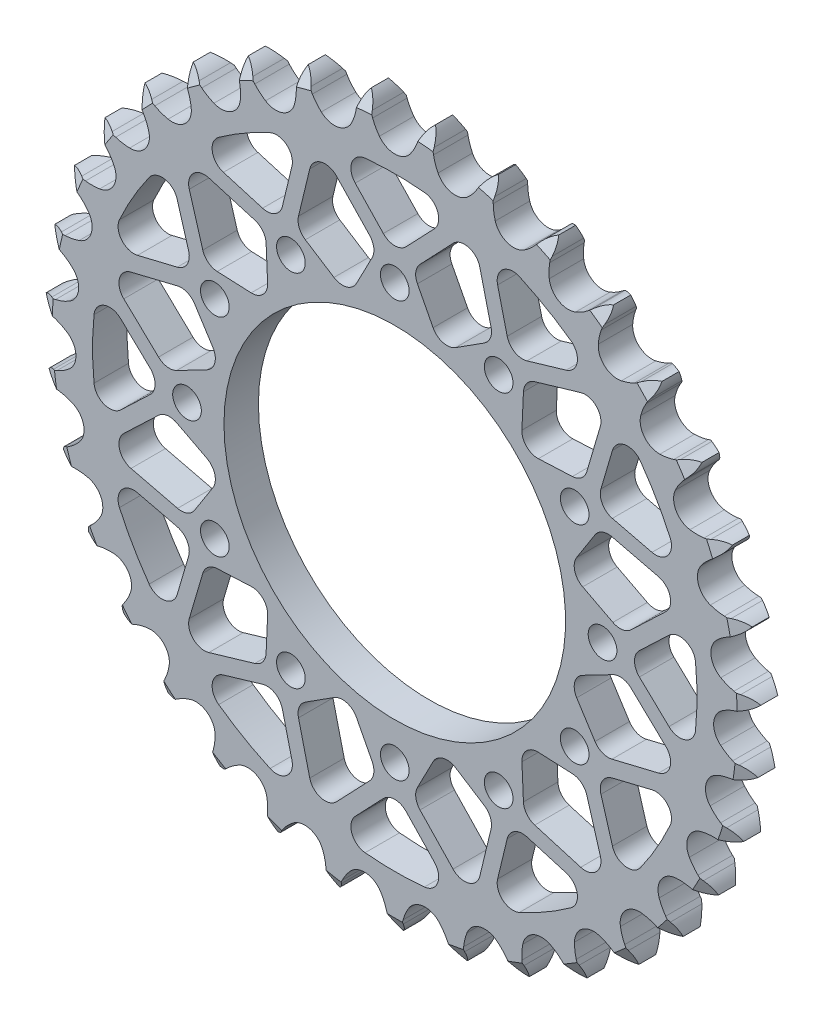
SolidWorks part; units mm, degrees
material "7075-T6 (SN)"
ref_plane "Front Plane" through (0, 0, 0) normal (0, 0, 1) x (1, 0, 0)
ref_plane "Top Plane" through (0, 0, 0) normal (0, 1, 0) x (1, 0, 0)
ref_plane "Right Plane" through (0, 0, 0) normal (1, 0, 0) x (0, 0, -1)
sketch "Work Sketch" plane through (0, 0, 0) normal (0, 0, 1) x (1, 0, 0)
  line L0 (0, 0) -> (0, 160.4542) construction
  line L1 (-112.0919, 70.8395) -> (87.2579, 70.8395) construction
  line L2 (5.0903, 120.8822) -> (5.0903, 112.9699) construction
  line L3 (-12.8497, 74.6356) -> (16.7256, 74.6356) construction
  line L4 (5.0903, 74.6356) -> (-6.074, 66.3097) construction
  line L5 (5.0903, 74.6356) -> (-4.641, 71.0332) construction
  line L6 (-4.641, 71.0332) -> (-6.9559, 77.2865)
  line L7 (-11.5114, 69.8433) -> (-7.1525, 69.8433) construction
  line L8 (-11.0678, 124.7602) -> (-11.0678, 110.2345) construction
  line L9 (0, 0) -> (-3.8324, 42.5811) construction
  circle A0 centre (0, 0) radius 70.8395
  circle A1 centre (0, 70.8395) radius 4.0088
  arc A2 (-4.641, 71.0332) -> (-3.2136, 68.4429) centre (5.0682, 74.6949) ccw
  circle A3 centre (-11.0678, 69.8433) radius 6.4401
  point P23 (-3.2136, 68.4429)
  dimension "D1" = 141.6789
  dimension "D8" = 10.3767
  dimension "D2" = 8.0177
  dimension "D3" = 5.0903
  dimension "D4" = 3.7962
  dimension "D5" = 36.714
  dimension "D6" = 16.4
  dimension "D7" = 10.3767
  dimension "D9" = 0.9961
  dimension "D10" = 11.0678
  dimension "D11" = 5.143
sketch "Teeth Sketch" plane through (0, 0, 0) normal (0, 0, 1) x (1, 0, 0)
  line L0 (5.0282, 72.0792) -> (4.641, 71.0332)
  line L1 (-8.3399, 92.6643) -> (-5.3292, 59.2127) construction
  line L2 (0, 0) -> (-12.1309, 132.2) construction
  line L3 (7.9229, 71.8186) -> (8.1171, 70.7203)
  line L4 (17927.8618, -199194.8588) -> (-17931.6941, 199237.4399) construction
  line L5 (0, 146.3285) -> (0, 56.9858) construction
  line L6 (17.8176, 70.023) -> (17.2498, 69.063)
  line L7 (0, -200000) -> (0, 200160.4542) construction
  line L8 (20.6192, 69.2498) -> (20.6142, 68.1345)
  line L9 (-4.641, 71.0332) -> (-6.9559, 77.2865) construction
  line L10 (43.6371, 57.589) -> (43.2405, 56.5465)
  line L11 (-5.0282, 72.0792) -> (-4.641, 71.0332)
  line L12 (30.0344, 65.7163) -> (29.3043, 64.873)
  line L13 (32.6529, 64.4552) -> (32.4488, 63.3587)
  line L14 (41.2858, 59.2973) -> (40.4169, 58.598)
  line L15 (51.2103, 50.9725) -> (50.2305, 50.4396)
  line L16 (53.2187, 48.8718) -> (52.6424, 47.9169)
  line L17 (59.4888, 41.0094) -> (58.4296, 40.66)
  line L18 (61.0899, 38.5838) -> (60.3523, 37.7472)
  line L19 (65.8553, 29.7283) -> (64.7507, 29.5736)
  line L20 (66.9976, 27.0558) -> (66.1224, 26.3643)
  line L21 (70.1052, 17.4916) -> (68.9907, 17.5366)
  line L22 (70.7519, 14.6581) -> (69.7673, 14.134)
  line L23 (72.1018, 4.6927) -> (71.0133, 4.9361)
  line L24 (72.2322, 1.7893) -> (71.1699, 1.4494)
  line L25 (71.781, -8.2569) -> (70.7534, -7.8232)
  line L26 (71.3909, -11.137) -> (70.2849, -11.2818)
  line L27 (69.1531, -20.9412) -> (68.2195, -20.331)
  line L28 (68.255, -23.7054) -> (67.141, -23.6503)
  line L29 (64.3026, -32.9525) -> (63.493, -32.1853)
  line L30 (62.9254, -35.5118) -> (61.8391, -35.2587)
  line L31 (57.3853, -43.9046) -> (56.7257, -43.0052)
  line L32 (55.5732, -46.1769) -> (54.5496, -45.7339)
  line L33 (48.6237, -53.4456) -> (48.1352, -52.4428)
  line L34 (46.435, -55.3578) -> (45.5069, -54.7392)
  line L35 (38.2992, -61.2688) -> (37.9976, -60.1949)
  line L36 (35.8042, -62.7594) -> (35.0015, -61.985)
  line L37 (26.7437, -67.1227) -> (26.6388, -66.0123)
  line L38 (24.0227, -68.144) -> (23.3712, -67.2387)
  line L39 (14.3287, -70.8193) -> (14.4237, -69.708)
  line L40 (11.4691, -71.3383) -> (10.9896, -70.3312)
  line L41 (1.4532, -72.2397) -> (1.7451, -71.1632)
  line L42 (-1.4532, -72.2397) -> (-1.7451, -71.1632)
  line L43 (-11.4691, -71.3383) -> (-10.9896, -70.3312)
  line L44 (-14.3287, -70.8193) -> (-14.4237, -69.708)
  line L45 (-24.0227, -68.144) -> (-23.3712, -67.2387)
  line L46 (-26.7437, -67.1227) -> (-26.6388, -66.0123)
  line L47 (-35.8042, -62.7594) -> (-35.0015, -61.985)
  line L48 (-38.2992, -61.2688) -> (-37.9976, -60.1949)
  line L49 (-46.435, -55.3578) -> (-45.5069, -54.7392)
  line L50 (-48.6237, -53.4456) -> (-48.1352, -52.4428)
  line L51 (-55.5732, -46.1769) -> (-54.5496, -45.7339)
  line L52 (-57.3853, -43.9046) -> (-56.7257, -43.0052)
  line L53 (-62.9254, -35.5118) -> (-61.8391, -35.2587)
  line L54 (-64.3026, -32.9525) -> (-63.493, -32.1853)
  line L55 (-68.255, -23.7054) -> (-67.141, -23.6503)
  line L56 (-69.1531, -20.9412) -> (-68.2195, -20.331)
  line L57 (-71.3909, -11.137) -> (-70.2849, -11.2818)
  line L58 (-71.781, -8.2569) -> (-70.7534, -7.8232)
  line L59 (-72.2322, 1.7893) -> (-71.1699, 1.4494)
  line L60 (-72.1018, 4.6927) -> (-71.0133, 4.9361)
  line L61 (-70.7519, 14.6581) -> (-69.7673, 14.134)
  line L62 (-70.1052, 17.4916) -> (-68.9907, 17.5366)
  line L63 (-66.9976, 27.0558) -> (-66.1224, 26.3643)
  line L64 (-65.8553, 29.7283) -> (-64.7507, 29.5736)
  line L65 (-61.0899, 38.5838) -> (-60.3523, 37.7472)
  line L66 (-59.4888, 41.0094) -> (-58.4296, 40.66)
  line L67 (-53.2187, 48.8718) -> (-52.6424, 47.9169)
  line L68 (-51.2103, 50.9725) -> (-50.2305, 50.4396)
  line L69 (-43.6371, 57.589) -> (-43.2405, 56.5465)
  line L70 (-41.2858, 59.2973) -> (-40.4169, 58.598)
  line L71 (-32.6529, 64.4552) -> (-32.4488, 63.3587)
  line L72 (-30.0344, 65.7163) -> (-29.3043, 64.873)
  line L73 (-20.6192, 69.2498) -> (-20.6142, 68.1345)
  line L74 (-17.8176, 70.023) -> (-17.2498, 69.063)
  line L75 (-7.9229, 71.8186) -> (-8.1171, 70.7203)
  arc A0 (-6.856, 74.7153) -> (-5.0282, 72.0792) centre (-11.0678, 69.8433) cw
  circle A1 centre (-11.0678, 69.8433) radius 6.4401 construction
  arc A2 (-3.2136, 68.4429) -> (-4.641, 71.0332) centre (5.0682, 74.6949) cw
  arc A3 (-4.641, 71.0332) -> (-3.2136, 68.4429) centre (5.0682, 74.6949) ccw construction
  circle A4 centre (0, 70.8395) radius 4.0088 construction
  arc A5 (-3.2136, 68.4429) -> (3.2136, 68.4429) centre (0, 70.8395) ccw
  arc A6 (3.2136, 68.4429) -> (4.641, 71.0332) centre (-5.0682, 74.6949) ccw
  arc A7 (6.856, 74.7153) -> (5.0282, 72.0792) centre (11.0678, 69.8433) ccw
  arc A8 (6.5951, 74.7388) -> (7.9229, 71.8186) centre (1.5811, 70.6972) cw
  arc A9 (9.059, 67.9168) -> (8.1171, 70.7203) centre (18.324, 72.5896) cw
  arc A10 (9.059, 67.9168) -> (15.3829, 66.7692) centre (12.6489, 69.701) ccw
  arc A11 (15.3829, 66.7692) -> (17.2498, 69.063) centre (8.3506, 74.3995) ccw
  arc A12 (20.0867, 72.2905) -> (17.8176, 70.023) centre (23.3609, 66.7447) ccw
  arc A13 (19.8343, 72.3601) -> (20.6192, 69.2498) centre (14.1792, 69.2787) cw
  arc A14 (21.0404, 65.2078) -> (20.6142, 68.1345) centre (30.9909, 68.1512) cw
  arc A15 (21.0404, 65.2078) -> (27.0578, 62.9494) centre (24.8912, 66.3224) ccw
  arc A16 (27.0578, 62.9494) -> (29.3043, 64.873) centre (21.5009, 71.7128) ccw
  arc A17 (32.6719, 67.5421) -> (30.0344, 65.7163) centre (34.9032, 61.5008) ccw
  arc A18 (32.4359, 67.6557) -> (32.6529, 64.4552) centre (26.3215, 65.6336) cw
  arc A19 (32.3456, 60.403) -> (32.4488, 63.3587) centre (42.6617, 61.5223) cw
  arc A20 (32.3456, 60.403) -> (37.863, 57.1065) centre (36.3335, 60.812) ccw
  arc A21 (37.863, 57.1065) -> (40.4169, 58.598) centre (33.9602, 66.7212) ccw
  arc A22 (44.207, 60.6229) -> (41.2858, 59.2973) centre (45.3237, 54.2803) ccw
  arc A23 (43.9951, 60.7768) -> (43.6371, 57.589) centre (37.6178, 59.8789) cw
  arc A24 (42.6112, 53.6567) -> (43.2405, 56.5465) centre (52.9614, 52.9161) cw
  arc A25 (42.6112, 53.6567) -> (47.4513, 49.428) centre (46.608, 53.3472) ccw
  arc A26 (47.4513, 49.428) -> (50.2305, 50.4396) centre (45.328, 59.5852) ccw
  arc A27 (54.3212, 51.7552) -> (51.2103, 50.9725) centre (54.2875, 45.3151) ccw
  arc A28 (54.1402, 51.9445) -> (53.2187, 48.8718) centre (47.7051, 52.1997) cw
  arc A29 (51.5072, 45.1859) -> (52.6424, 47.9169) centre (61.5588, 42.6091) cw
  arc A30 (51.5072, 45.1859) -> (55.5144, 40.161) centre (55.3845, 44.1677) ccw
  arc A31 (55.5144, 40.161) -> (58.4296, 40.66) centre (55.2389, 50.534) ccw
  arc A32 (62.6894, 41.224) -> (59.4888, 41.0094) centre (61.5064, 34.8935) ccw
  arc A33 (62.5452, 41.4426) -> (61.0899, 38.5838) centre (56.2591, 42.8428) cw
  arc A34 (58.7477, 35.2628) -> (60.3523, 37.7472) centre (68.1777, 30.9326) cw
  arc A35 (58.7477, 35.2628) -> (61.7933, 29.6031) centre (62.3809, 33.5686) ccw
  arc A36 (61.7933, 29.6031) -> (64.7507, 29.5736) centre (63.3744, 39.8586) ccw
  arc A37 (69.0428, 29.3679) -> (65.8553, 29.7283) centre (66.7484, 23.3503) ccw
  arc A38 (68.9399, 29.6087) -> (66.9976, 27.0558) centre (63.0048, 32.1088) cw
  arc A39 (64.1, 24.2063) -> (66.1224, 26.3643) centre (72.6052, 18.2619) cw
  arc A40 (64.1, 24.2063) -> (66.0861, 18.0937) centre (67.3723, 21.8906) ccw
  arc A41 (66.0861, 18.0937) -> (68.9907, 17.5366) centre (69.4729, 27.9021) ccw
  arc A42 (73.1771, 16.5679) -> (70.1052, 17.4916) centre (69.8451, 11.0567) ccw
  arc A43 (73.1188, 16.8232) -> (70.7519, 14.6581) centre (67.7256, 20.3429) cw
  arc A44 (67.3921, 12.3718) -> (69.7673, 14.134) centre (74.6992, 5.0042) cw
  arc A45 (67.3921, 12.3718) -> (68.2548, 6.0028) centre (70.1983, 9.509) ccw
  arc A46 (68.2548, 6.0028) -> (71.0133, 4.9361) centre (73.3386, 15.0489) ccw
  arc A47 (74.9595, 3.2354) -> (72.1018, 4.6927) centre (70.6969, -1.5923) ccw
  arc A48 (74.9477, 3.497) -> (72.2322, 1.7893) centre (70.2696, 7.9231) cw
  arc A49 (68.5181, 0.1397) -> (71.1699, 1.4494) centre (74.3923, -8.4143) cw
  arc A50 (68.5181, 0.1397) -> (68.2298, -6.281) centre (70.7681, -3.1782) ccw
  arc A51 (68.2298, -6.281) -> (70.7534, -7.8232) centre (74.8471, 1.7119) ccw
  arc A52 (74.3325, -10.2012) -> (71.781, -8.2569) centre (69.2765, -14.1901) ccw
  arc A53 (74.3677, -9.9416) -> (71.3909, -11.137) centre (70.555, -4.7513) cw
  arc A54 (67.442, -12.097) -> (70.2849, -11.2818) centre (71.6944, -21.5623) cw
  arc A55 (67.442, -12.097) -> (66.0118, -18.363) centre (69.0634, -15.7633) ccw
  arc A56 (66.0118, -18.363) -> (68.2195, -20.331) centre (73.9499, -11.6801) ccw
  arc A57 (71.3165, -23.3098) -> (69.1531, -20.9412) centre (65.6294, -26.3319) ccw
  arc A58 (71.3974, -23.0607) -> (68.255, -23.7054) centre (68.5728, -17.2731) cw
  arc A59 (64.1981, -23.9448) -> (67.141, -23.6503) centre (66.6921, -34.0173) cw
  arc A60 (64.1981, -23.9448) -> (61.6721, -29.8547) centre (65.1388, -27.8417) ccw
  arc A61 (61.6721, -29.8547) -> (63.493, -32.1853) centre (70.676, -24.6966) ccw
  arc A62 (66.0083, -35.6693) -> (64.3026, -32.9525) centre (59.873, -37.6273) ccw
  arc A63 (66.1324, -35.4386) -> (62.9254, -35.5118) centre (64.3866, -29.2396) cw
  arc A64 (58.8909, -35.023) -> (61.8391, -35.2587) centre (59.5463, -45.379) cw
  arc A65 (58.8909, -35.023) -> (55.3502, -40.3869) centre (59.1207, -39.0252) ccw
  arc A66 (55.3502, -40.3869) -> (56.7257, -43.0052) centre (65.1304, -36.9194) ccw
  arc A67 (58.5785, -46.8823) -> (57.3853, -43.9046) centre (52.1922, -47.7133) ccw
  arc A68 (58.7418, -46.6775) -> (55.5732, -46.1769) centre (58.1309, -40.2664) cw
  arc A69 (51.6909, -44.9755) -> (54.5496, -45.7339) centre (50.4867, -55.2821) cw
  arc A70 (51.6909, -44.9755) -> (47.2494, -49.6211) centre (51.2024, -48.9545) ccw
  arc A71 (47.2494, -49.6211) -> (48.1352, -52.4428) centre (57.4915, -47.9556) ccw
  arc A72 (49.266, -56.5885) -> (48.6237, -53.4456) centre (42.8339, -56.2658) ccw
  arc A73 (49.4632, -56.4161) -> (46.435, -55.3578) centre (50.0069, -49.999) cw
  arc A74 (42.8296, -53.4825) -> (45.5069, -54.7392) centre (39.8043, -63.4085) cw
  arc A75 (42.8296, -53.4825) -> (37.6299, -57.2603) centre (41.6384, -57.3103) ccw
  arc A76 (37.6299, -57.2603) -> (37.9976, -60.1949) centre (48.0048, -57.4505) ccw
  arc A77 (38.37, -64.4758) -> (38.2992, -61.2688) centre (32.0989, -63.0099) ccw
  arc A78 (38.5948, -64.3415) -> (35.8042, -62.7594) centre (40.2756, -58.1246) cw
  arc A79 (32.5916, -60.2706) -> (35.0015, -61.985) centre (27.8426, -69.4968) cw
  arc A80 (32.5916, -60.2706) -> (26.8009, -63.0592) centre (30.7361, -63.8241) ccw
  arc A81 (26.8009, -63.0592) -> (26.6388, -66.0123) centre (36.9752, -65.0988) ccw
  arc A82 (26.2407, -70.2909) -> (26.7437, -67.1227) centre (20.3322, -67.7288) ccw
  arc A83 (26.4859, -70.1989) -> (24.0227, -68.144) centre (29.2498, -64.382) cw
  arc A84 (21.3061, -65.1215) -> (23.3712, -67.2387) centre (14.9861, -73.3515) cw
  arc A85 (21.3061, -65.1215) -> (15.1105, -66.8313) centre (18.8459, -68.2866) ccw
  arc A86 (15.1105, -66.8313) -> (14.4237, -69.708) centre (24.7571, -70.6548) ccw
  arc A87 (13.2681, -73.8468) -> (14.3287, -70.8193) centre (7.912, -70.2708) ccw
  arc A88 (13.5258, -73.8) -> (11.4691, -71.3383) centre (17.2839, -68.5701) cw
  arc A89 (9.3358, -67.8793) -> (10.9896, -70.3312) centre (1.6478, -74.8485) cw
  arc A90 (9.3358, -67.8793) -> (2.9345, -68.4554) centre (6.35, -70.5543) ccw
  arc A91 (2.9345, -68.4554) -> (1.7451, -71.1632) centre (11.7434, -73.9399) ccw
  arc A92 (-0.131, -75.0291) -> (1.4532, -72.2397) centre (-4.7625, -70.5543) ccw
  arc A93 (0.131, -75.0291) -> (-1.4532, -72.2397) centre (4.7625, -70.5543) cw
  arc A94 (-2.9345, -68.4554) -> (-1.7451, -71.1632) centre (-11.7434, -73.9399) cw
  arc A95 (-2.9345, -68.4554) -> (-9.3358, -67.8793) centre (-6.35, -70.5543) ccw
  arc A96 (-9.3358, -67.8793) -> (-10.9896, -70.3312) centre (-1.6478, -74.8485) ccw
  arc A97 (-13.5258, -73.8) -> (-11.4691, -71.3383) centre (-17.2839, -68.5701) ccw
  arc A98 (-13.2681, -73.8468) -> (-14.3287, -70.8193) centre (-7.912, -70.2708) cw
  arc A99 (-15.1105, -66.8313) -> (-14.4237, -69.708) centre (-24.7571, -70.6548) cw
  arc A100 (-15.1105, -66.8313) -> (-21.3061, -65.1215) centre (-18.8459, -68.2866) ccw
  arc A101 (-21.3061, -65.1215) -> (-23.3712, -67.2387) centre (-14.9861, -73.3515) ccw
  arc A102 (-26.4859, -70.1989) -> (-24.0227, -68.144) centre (-29.2498, -64.382) ccw
  arc A103 (-26.2407, -70.2909) -> (-26.7437, -67.1227) centre (-20.3322, -67.7288) cw
  arc A104 (-26.8009, -63.0592) -> (-26.6388, -66.0123) centre (-36.9752, -65.0988) cw
  arc A105 (-26.8009, -63.0592) -> (-32.5916, -60.2706) centre (-30.7361, -63.8241) ccw
  arc A106 (-32.5916, -60.2706) -> (-35.0015, -61.985) centre (-27.8426, -69.4968) ccw
  arc A107 (-38.5948, -64.3415) -> (-35.8042, -62.7594) centre (-40.2756, -58.1246) ccw
  arc A108 (-38.37, -64.4758) -> (-38.2992, -61.2688) centre (-32.0989, -63.0099) cw
  arc A109 (-37.6299, -57.2603) -> (-37.9976, -60.1949) centre (-48.0048, -57.4505) cw
  arc A110 (-37.6299, -57.2603) -> (-42.8296, -53.4825) centre (-41.6384, -57.3103) ccw
  arc A111 (-42.8296, -53.4825) -> (-45.5069, -54.7392) centre (-39.8043, -63.4085) ccw
  arc A112 (-49.4632, -56.4161) -> (-46.435, -55.3578) centre (-50.0069, -49.999) ccw
  arc A113 (-49.266, -56.5885) -> (-48.6237, -53.4456) centre (-42.8339, -56.2658) cw
  arc A114 (-47.2494, -49.6211) -> (-48.1352, -52.4428) centre (-57.4915, -47.9556) cw
  arc A115 (-47.2494, -49.6211) -> (-51.6909, -44.9755) centre (-51.2024, -48.9545) ccw
  arc A116 (-51.6909, -44.9755) -> (-54.5496, -45.7339) centre (-50.4867, -55.2821) ccw
  arc A117 (-58.7418, -46.6775) -> (-55.5732, -46.1769) centre (-58.1309, -40.2664) ccw
  arc A118 (-58.5785, -46.8823) -> (-57.3853, -43.9046) centre (-52.1922, -47.7133) cw
  arc A119 (-55.3502, -40.3869) -> (-56.7257, -43.0052) centre (-65.1304, -36.9194) cw
  arc A120 (-55.3502, -40.3869) -> (-58.8909, -35.023) centre (-59.1207, -39.0252) ccw
  arc A121 (-58.8909, -35.023) -> (-61.8391, -35.2587) centre (-59.5463, -45.379) ccw
  arc A122 (-66.1324, -35.4386) -> (-62.9254, -35.5118) centre (-64.3866, -29.2396) ccw
  arc A123 (-66.0083, -35.6693) -> (-64.3026, -32.9525) centre (-59.873, -37.6273) cw
  arc A124 (-61.6721, -29.8547) -> (-63.493, -32.1853) centre (-70.676, -24.6966) cw
  arc A125 (-61.6721, -29.8547) -> (-64.1981, -23.9448) centre (-65.1388, -27.8417) ccw
  arc A126 (-64.1981, -23.9448) -> (-67.141, -23.6503) centre (-66.6921, -34.0173) ccw
  arc A127 (-71.3974, -23.0607) -> (-68.255, -23.7054) centre (-68.5728, -17.2731) ccw
  arc A128 (-71.3165, -23.3098) -> (-69.1531, -20.9412) centre (-65.6294, -26.3319) cw
  arc A129 (-66.0118, -18.363) -> (-68.2195, -20.331) centre (-73.9499, -11.6801) cw
  arc A130 (-66.0118, -18.363) -> (-67.442, -12.097) centre (-69.0634, -15.7633) ccw
  arc A131 (-67.442, -12.097) -> (-70.2849, -11.2818) centre (-71.6944, -21.5623) ccw
  arc A132 (-74.3677, -9.9416) -> (-71.3909, -11.137) centre (-70.555, -4.7513) ccw
  arc A133 (-74.3325, -10.2012) -> (-71.781, -8.2569) centre (-69.2765, -14.1901) cw
  arc A134 (-68.2298, -6.281) -> (-70.7534, -7.8232) centre (-74.8471, 1.7119) cw
  arc A135 (-68.2298, -6.281) -> (-68.5181, 0.1397) centre (-70.7681, -3.1782) ccw
  arc A136 (-68.5181, 0.1397) -> (-71.1699, 1.4494) centre (-74.3923, -8.4143) ccw
  arc A137 (-74.9477, 3.497) -> (-72.2322, 1.7893) centre (-70.2696, 7.9231) ccw
  arc A138 (-74.9595, 3.2354) -> (-72.1018, 4.6927) centre (-70.6969, -1.5923) cw
  arc A139 (-68.2548, 6.0028) -> (-71.0133, 4.9361) centre (-73.3386, 15.0489) cw
  arc A140 (-68.2548, 6.0028) -> (-67.3921, 12.3718) centre (-70.1983, 9.509) ccw
  arc A141 (-67.3921, 12.3718) -> (-69.7673, 14.134) centre (-74.6992, 5.0042) ccw
  arc A142 (-73.1188, 16.8232) -> (-70.7519, 14.6581) centre (-67.7256, 20.3429) ccw
  arc A143 (-73.1771, 16.5679) -> (-70.1052, 17.4916) centre (-69.8451, 11.0567) cw
  arc A144 (-66.0861, 18.0937) -> (-68.9907, 17.5366) centre (-69.4729, 27.9021) cw
  arc A145 (-66.0861, 18.0937) -> (-64.1, 24.2063) centre (-67.3723, 21.8906) ccw
  arc A146 (-64.1, 24.2063) -> (-66.1224, 26.3643) centre (-72.6052, 18.2619) ccw
  arc A147 (-68.9399, 29.6087) -> (-66.9976, 27.0558) centre (-63.0048, 32.1088) ccw
  arc A148 (-69.0428, 29.3679) -> (-65.8553, 29.7283) centre (-66.7484, 23.3503) cw
  arc A149 (-61.7933, 29.6031) -> (-64.7507, 29.5736) centre (-63.3744, 39.8586) cw
  arc A150 (-61.7933, 29.6031) -> (-58.7477, 35.2628) centre (-62.3809, 33.5686) ccw
  arc A151 (-58.7477, 35.2628) -> (-60.3523, 37.7472) centre (-68.1777, 30.9326) ccw
  arc A152 (-62.5452, 41.4426) -> (-61.0899, 38.5838) centre (-56.2591, 42.8428) ccw
  arc A153 (-62.6894, 41.224) -> (-59.4888, 41.0094) centre (-61.5064, 34.8935) cw
  arc A154 (-55.5144, 40.161) -> (-58.4296, 40.66) centre (-55.2389, 50.534) cw
  arc A155 (-55.5144, 40.161) -> (-51.5072, 45.1859) centre (-55.3845, 44.1677) ccw
  arc A156 (-51.5072, 45.1859) -> (-52.6424, 47.9169) centre (-61.5588, 42.6091) ccw
  arc A157 (-54.1402, 51.9445) -> (-53.2187, 48.8718) centre (-47.7051, 52.1997) ccw
  arc A158 (-54.3212, 51.7552) -> (-51.2103, 50.9725) centre (-54.2875, 45.3151) cw
  arc A159 (-47.4513, 49.428) -> (-50.2305, 50.4396) centre (-45.328, 59.5852) cw
  arc A160 (-47.4513, 49.428) -> (-42.6112, 53.6567) centre (-46.608, 53.3472) ccw
  arc A161 (-42.6112, 53.6567) -> (-43.2405, 56.5465) centre (-52.9614, 52.9161) ccw
  arc A162 (-43.9951, 60.7768) -> (-43.6371, 57.589) centre (-37.6178, 59.8789) ccw
  arc A163 (-44.207, 60.6229) -> (-41.2858, 59.2973) centre (-45.3237, 54.2803) cw
  arc A164 (-37.863, 57.1065) -> (-40.4169, 58.598) centre (-33.9602, 66.7212) cw
  arc A165 (-37.863, 57.1065) -> (-32.3456, 60.403) centre (-36.3335, 60.812) ccw
  arc A166 (-32.3456, 60.403) -> (-32.4488, 63.3587) centre (-42.6617, 61.5223) ccw
  arc A167 (-32.4359, 67.6557) -> (-32.6529, 64.4552) centre (-26.3215, 65.6336) ccw
  arc A168 (-32.6719, 67.5421) -> (-30.0344, 65.7163) centre (-34.9032, 61.5008) cw
  arc A169 (-27.0578, 62.9494) -> (-29.3043, 64.873) centre (-21.5009, 71.7128) cw
  arc A170 (-27.0578, 62.9494) -> (-21.0404, 65.2078) centre (-24.8912, 66.3224) ccw
  arc A171 (-21.0404, 65.2078) -> (-20.6142, 68.1345) centre (-30.9909, 68.1512) ccw
  arc A172 (-19.8343, 72.3601) -> (-20.6192, 69.2498) centre (-14.1792, 69.2787) ccw
  arc A173 (-20.0867, 72.2905) -> (-17.8176, 70.023) centre (-23.3609, 66.7447) cw
  arc A174 (-15.3829, 66.7692) -> (-17.2498, 69.063) centre (-8.3506, 74.3995) cw
  arc A175 (-15.3829, 66.7692) -> (-9.059, 67.9168) centre (-12.6489, 69.701) ccw
  arc A176 (-9.059, 67.9168) -> (-8.1171, 70.7203) centre (-18.324, 72.5896) ccw
  arc A177 (-6.5951, 74.7388) -> (-7.9229, 71.8186) centre (-1.5811, 70.6972) ccw
  point P77 (0, 0)
  dimension "D1" = 5.143
  dimension "D2" = 5.243
  dimension "D3" = 35
extrude "Extrusion" add sketch "Teeth Sketch" along normal blind 7.2136 contours A0 region at (0, 0, 0)
sketch "Sketch1" plane through (0, 0, 0) normal (0, 0, -1) x (-1, 0, 0)
  circle A0 centre (0, 0) radius 78.9443
  circle A1 centre (0, 0) radius 35.7643
  dimension "D1" = 43.18
extrude "Cut-Extrude" cut sketch "Sketch1" against normal through all both and the other way through all contours A1
ref_axis "Axis2" through (0, 0, -0.3607) along (0, 0, 1)
ref_axis "Axis1" [suppressed] through (0, 0, 7.2136) along (0, 0, -1)
ref_plane "Sprocket Center Plane" through (0, 0, 3.6068) normal (0, 0, 1) x (1, 0, 0)
sketch "Pitch Circle" plane through (0, 0, 3.6068) normal (0, 0, -1) x (-1, 0, 0)
  circle A0 centre (0, 0) radius 82.9531 construction
  dimension "D1" = 165.9063
sketch "Chain Pitch Circle" plane through (0, 0, 0) normal (0, 0, -1) x (-1, 0, 0)
  circle A0 centre (0, 0) radius 82.9531 construction
  dimension "D1" = 165.9063
ref_plane "Center Plane" through (0, 0, 3.6068) normal (0, 0, 1) x (1, 0, 0)
hole_wizard "Ø6.0mm Dowel Hole1" positions "Sketch7" profile "Sketch8" hole size "Ø6.0" standard "ANSI Metric" end condition through all
sketch "Sketch7" plane through (0, 0, 7.2136) normal (0, 0, 1) x (1, 0, 0)
  point P0 (-43.5, 0)
  dimension "D1" = 43.5
sketch "Sketch8" plane through (-43.5, 0, 7.2136) normal (1, 0, 0) x (0, -1, 0)
  line L0 (0, 0) -> (0, 7.2136)
  line L1 (0, 7.2136) -> (3, 7.2136)
  line L2 (3, 7.2136) -> (3, 0)
  line L5 (3, 0) -> (0, 0)
  line L11 (0, -6.35) -> (0, 107.95) construction
  dimension "Thru Hole Dia." = 6
  dimension "Thru Hole Depth" = 7.2136
pattern_circular "CirPattern1" count 12 over 360 about axis through (0, 0, 7.2136) along (0, 0, -1) of "Ø6.0mm Dowel Hole1" reverse direction yes
ref_plane "Plane1" through (0, 0, 3.6068) normal (0, 0, -1) x (-1, 0, 0)
sketch "Sketch9" plane through (0, 0, 0) normal (0, 0, 1) x (1, 0, 0)
  line L0 (-43.5, 0) -> (-63.2746, 0) construction
  line L1 (-61.9966, 12.6533) -> (-48.707, 0)
  line L2 (-61.9966, -12.6533) -> (-48.707, 0)
  line L11 (-43.5, 0) -> (-37.6721, 21.75) construction
  line L13 (-61.1186, 16.3767) -> (-36.1404, 9.6838) construction
  line L18 (-43.1887, 20.7127) -> (-36.1404, 9.6838)
  line L19 (-47.7589, 3.6566) -> (-36.1404, 9.6838)
  line L20 (-43.1887, 20.7127) -> (-61.1186, 16.3767)
  line L21 (-47.7589, 3.6566) -> (-61.1186, 16.3767)
  circle A0 centre (0, 0) radius 66.8306 construction
  arc A1 (-15.3829, 66.7692) -> (-9.059, 67.9168) centre (-12.6489, 69.701) ccw construction
  circle A2 centre (-43.5, 0) radius 3 construction
  circle A3 centre (-43.5, 0) radius 5.207
  circle A4 centre (-37.6721, 21.75) radius 3 construction
  circle A6 centre (-37.6721, 21.75) radius 5.207
  circle A196 centre (0, 0) radius 63.2746
  circle A197 centre (0, 0) radius 35.7643 construction
  circle A198 centre (0, 0) radius 35.7643
  circle A199 centre (0, 0) radius 37.4153 construction
  point P17 (-40.5861, 10.875)
  dimension "D1" = 3.556
  dimension "D2" = 1.651
  dimension "D3" = 10.414
  dimension "D4" = 3.302
extrude "Cut-Extrude2" cut sketch "Sketch9" along normal through all contours L1 A196 L2 | L21 L19 L18 L20 region at (-58.1293, 0, 0) region at (-47.5776, 12.7484, 0)
fillet "Fillet2" radius 3.302 7 edges at (-61.1186, 16.3767, 3.6068) (-36.1404, 9.6838, 3.6068) (-47.7589, 3.6566, 3.6068) (-43.1887, 20.7127, 3.6068) (-61.9966, -12.6533, 3.6068) (-48.707, 0, 3.6068) (-61.9966, 12.6533, 3.6068)
pattern_circular "CirPattern3" count 12 over 360 about axis through (0, 0, 7.2136) along (0, 0, -1) of "Cut-Extrude2", "Fillet2"
sketch "Sketch14" plane through (0, 0, 7.2136) normal (0, 0, 1) x (1, 0, 0)
  line L0 (-45.6677, -4.7414) -> (-39.3483, -8.0197) construction
  line L1 (-38.2956, 5.9905) -> (-37.9766, 6.1559)
  line L2 (-43.5, 0) -> (-38.293, 0) construction
  line L3 (-38.2956, -5.9905) -> (-37.9766, -6.1559)
  line L4 (-30.1697, 24.3357) -> (-29.8108, 24.3195)
  line L5 (-36.1602, 13.9599) -> (-35.9667, 13.6571)
  line L6 (-13.9599, 36.1602) -> (-13.6571, 35.9667)
  line L7 (-24.3357, 30.1697) -> (-24.3195, 29.8108)
  line L8 (5.9905, 38.2956) -> (6.1559, 37.9766)
  line L9 (-5.9905, 38.2956) -> (-6.1559, 37.9766)
  line L10 (24.3357, 30.1697) -> (24.3195, 29.8108)
  line L11 (13.9599, 36.1602) -> (13.6571, 35.9667)
  line L12 (36.1602, 13.9599) -> (35.9667, 13.6571)
  line L13 (30.1697, 24.3357) -> (29.8108, 24.3195)
  line L14 (38.2956, -5.9905) -> (37.9766, -6.1559)
  line L15 (38.2956, 5.9905) -> (37.9766, 6.1559)
  line L16 (30.1697, -24.3357) -> (29.8108, -24.3195)
  line L17 (36.1602, -13.9599) -> (35.9667, -13.6571)
  line L18 (13.9599, -36.1602) -> (13.6571, -35.9667)
  line L19 (24.3357, -30.1697) -> (24.3195, -29.8108)
  line L20 (-5.9905, -38.2956) -> (-6.1559, -37.9766)
  line L21 (5.9905, -38.2956) -> (6.1559, -37.9766)
  line L22 (-24.3357, -30.1697) -> (-24.3195, -29.8108)
  line L23 (-13.9599, -36.1602) -> (-13.6571, -35.9667)
  line L24 (-36.1602, -13.9599) -> (-35.9667, -13.6571)
  line L25 (-30.1697, -24.3357) -> (-29.8108, -24.3195)
  arc A0 (-39.0014, -2.6222) -> (-39.0014, 2.6222) centre (-43.5, 0) ccw
  circle A1 centre (0, 0) radius 35.7643 construction
  arc A2 (-37.9766, -6.1559) -> (-39.0014, -2.6222) centre (-36.807, -3.9013) cw
  arc A3 (-38.2956, 5.9905) -> (-36.1602, 13.9599) centre (-40.8688, 10.9508) ccw
  arc A4 (-38.2956, 5.9905) -> (-36.1602, 13.9599) centre (-40.8688, 10.9508) ccw
  arc A5 (-37.9766, 6.1559) -> (-39.0014, 2.6222) centre (-36.807, 3.9013) ccw
  circle A6 centre (0, 0) radius 35.7643
  arc A7 (-30.1697, 24.3357) -> (-24.3357, 30.1697) centre (-29.918, 29.918) ccw
  arc A8 (-29.8108, 24.3195) -> (-32.4651, 21.7716) centre (-29.9252, 21.7821) ccw
  arc A9 (-35.0873, 17.2299) -> (-32.4651, 21.7716) centre (-37.6721, 21.75) ccw
  arc A10 (-35.9667, 13.6571) -> (-35.0873, 17.2299) centre (-33.8264, 15.0249) cw
  arc A11 (-13.9599, 36.1602) -> (-5.9905, 38.2956) centre (-10.9508, 40.8688) ccw
  arc A12 (-13.6571, 35.9667) -> (-17.2299, 35.0873) centre (-15.0249, 33.8264) ccw
  arc A13 (-21.7716, 32.4651) -> (-17.2299, 35.0873) centre (-21.75, 37.6721) ccw
  arc A14 (-24.3195, 29.8108) -> (-21.7716, 32.4651) centre (-21.7821, 29.9252) cw
  arc A15 (5.9905, 38.2956) -> (13.9599, 36.1602) centre (10.9508, 40.8688) ccw
  arc A16 (6.1559, 37.9766) -> (2.6222, 39.0014) centre (3.9013, 36.807) ccw
  arc A17 (-2.6222, 39.0014) -> (2.6222, 39.0014) centre (0, 43.5) ccw
  arc A18 (-6.1559, 37.9766) -> (-2.6222, 39.0014) centre (-3.9013, 36.807) cw
  arc A19 (24.3357, 30.1697) -> (30.1697, 24.3357) centre (29.918, 29.918) ccw
  arc A20 (24.3195, 29.8108) -> (21.7716, 32.4651) centre (21.7821, 29.9252) ccw
  arc A21 (17.2299, 35.0873) -> (21.7716, 32.4651) centre (21.75, 37.6721) ccw
  arc A22 (13.6571, 35.9667) -> (17.2299, 35.0873) centre (15.0249, 33.8264) cw
  arc A23 (36.1602, 13.9599) -> (38.2956, 5.9905) centre (40.8688, 10.9508) ccw
  arc A24 (35.9667, 13.6571) -> (35.0873, 17.2299) centre (33.8264, 15.0249) ccw
  arc A25 (32.4651, 21.7716) -> (35.0873, 17.2299) centre (37.6721, 21.75) ccw
  arc A26 (29.8108, 24.3195) -> (32.4651, 21.7716) centre (29.9252, 21.7821) cw
  arc A27 (38.2956, -5.9905) -> (36.1602, -13.9599) centre (40.8688, -10.9508) ccw
  arc A28 (37.9766, -6.1559) -> (39.0014, -2.6222) centre (36.807, -3.9013) ccw
  arc A29 (39.0014, 2.6222) -> (39.0014, -2.6222) centre (43.5, 0) ccw
  arc A30 (37.9766, 6.1559) -> (39.0014, 2.6222) centre (36.807, 3.9013) cw
  arc A31 (30.1697, -24.3357) -> (24.3357, -30.1697) centre (29.918, -29.918) ccw
  arc A32 (29.8108, -24.3195) -> (32.4651, -21.7716) centre (29.9252, -21.7821) ccw
  arc A33 (35.0873, -17.2299) -> (32.4651, -21.7716) centre (37.6721, -21.75) ccw
  arc A34 (35.9667, -13.6571) -> (35.0873, -17.2299) centre (33.8264, -15.0249) cw
  arc A35 (13.9599, -36.1602) -> (5.9905, -38.2956) centre (10.9508, -40.8688) ccw
  arc A36 (13.6571, -35.9667) -> (17.2299, -35.0873) centre (15.0249, -33.8264) ccw
  arc A37 (21.7716, -32.4651) -> (17.2299, -35.0873) centre (21.75, -37.6721) ccw
  arc A38 (24.3195, -29.8108) -> (21.7716, -32.4651) centre (21.7821, -29.9252) cw
  arc A39 (-5.9905, -38.2956) -> (-13.9599, -36.1602) centre (-10.9508, -40.8688) ccw
  arc A40 (-6.1559, -37.9766) -> (-2.6222, -39.0014) centre (-3.9013, -36.807) ccw
  arc A41 (2.6222, -39.0014) -> (-2.6222, -39.0014) centre (0, -43.5) ccw
  arc A42 (6.1559, -37.9766) -> (2.6222, -39.0014) centre (3.9013, -36.807) cw
  arc A43 (-24.3357, -30.1697) -> (-30.1697, -24.3357) centre (-29.918, -29.918) ccw
  arc A44 (-24.3195, -29.8108) -> (-21.7716, -32.4651) centre (-21.7821, -29.9252) ccw
  arc A45 (-17.2299, -35.0873) -> (-21.7716, -32.4651) centre (-21.75, -37.6721) ccw
  arc A46 (-13.6571, -35.9667) -> (-17.2299, -35.0873) centre (-15.0249, -33.8264) cw
  arc A47 (-36.1602, -13.9599) -> (-38.2956, -5.9905) centre (-40.8688, -10.9508) ccw
  arc A48 (-35.9667, -13.6571) -> (-35.0873, -17.2299) centre (-33.8264, -15.0249) ccw
  arc A49 (-32.4651, -21.7716) -> (-35.0873, -17.2299) centre (-37.6721, -21.75) ccw
  arc A50 (-29.8108, -24.3195) -> (-32.4651, -21.7716) centre (-29.9252, -21.7821) cw
  point P10 (-41.0188, -4.5778)
  point P16 (-41.0188, 4.5778)
  point P144 (0, 0)
  dimension "D2" = 2.54
  dimension "D1" = 2.286
  dimension "D3" = 12
extrude "Cut-Extrude7" [suppressed] cut sketch "Sketch14" against normal through all
sketch "Sketch15" plane through (0, 0, 0) normal (0, 0, -1) x (-1, 0, 0)
  line L9 (-30.8009, 49.3753) -> (-28.037, 48.5615)
  line L10 (-28.037, 48.5615) -> (-27.3598, 51.362)
  line L11 (-48.5615, 28.037) -> (-49.3753, 30.8009)
  line L12 (-51.362, 27.3598) -> (-48.5615, 28.037)
  line L13 (-48.5615, 28.037) -> (-49.3753, 30.8009)
  line L14 (-51.362, 27.3598) -> (-48.5615, 28.037)
  line L15 (-46.8809, 9.8349) -> (-43.4148, 11.633)
  line L16 (-50.8663, 13.6296) -> (-46.8809, 9.8349)
  line L17 (-45.5175, 14.9231) -> (-50.8663, 13.6296)
  line L18 (-43.4148, 11.633) -> (-45.5175, 14.9231)
  line L19 (-46.8809, 9.8349) -> (-43.4148, 11.633)
  line L20 (-50.8663, 13.6296) -> (-46.8809, 9.8349)
  line L21 (-45.5175, 14.9231) -> (-50.8663, 13.6296)
  line L22 (-43.4148, 11.633) -> (-45.5175, 14.9231)
  line L23 (-37.2367, 37.2367) -> (-35.6825, 31.9577)
  line L24 (-35.6825, 31.9577) -> (-31.7819, 31.7819)
  line L25 (-31.7819, 31.7819) -> (-31.9577, 35.6825)
  line L26 (-31.9577, 35.6825) -> (-37.2367, 37.2367)
  line L27 (-1.9867, 58.1607) -> (0, 56.074)
  line L28 (0, 56.074) -> (1.9867, 58.1607)
  line L29 (-13.6296, 50.8663) -> (-14.9231, 45.5175)
  line L30 (-14.9231, 45.5175) -> (-11.633, 43.4148)
  line L31 (-11.633, 43.4148) -> (-9.8349, 46.8809)
  line L32 (-9.8349, 46.8809) -> (-13.6296, 50.8663)
  line L33 (27.3598, 51.362) -> (28.037, 48.5615)
  line L34 (28.037, 48.5615) -> (30.8009, 49.3753)
  line L35 (13.6296, 50.8663) -> (9.8349, 46.8809)
  line L36 (9.8349, 46.8809) -> (11.633, 43.4148)
  line L37 (11.633, 43.4148) -> (14.9231, 45.5175)
  line L38 (14.9231, 45.5175) -> (13.6296, 50.8663)
  line L39 (49.3753, 30.8009) -> (48.5615, 28.037)
  line L40 (48.5615, 28.037) -> (51.362, 27.3598)
  line L41 (37.2367, 37.2367) -> (31.9577, 35.6825)
  line L42 (31.9577, 35.6825) -> (31.7819, 31.7819)
  line L43 (31.7819, 31.7819) -> (35.6825, 31.9577)
  line L44 (35.6825, 31.9577) -> (37.2367, 37.2367)
  line L45 (58.1607, 1.9867) -> (56.074, 0)
  line L46 (56.074, 0) -> (58.1607, -1.9867)
  line L47 (50.8663, 13.6296) -> (45.5175, 14.9231)
  line L48 (45.5175, 14.9231) -> (43.4148, 11.633)
  line L49 (43.4148, 11.633) -> (46.8809, 9.8349)
  line L50 (46.8809, 9.8349) -> (50.8663, 13.6296)
  line L51 (51.362, -27.3598) -> (48.5615, -28.037)
  line L52 (48.5615, -28.037) -> (49.3753, -30.8009)
  line L53 (50.8663, -13.6296) -> (46.8809, -9.8349)
  line L54 (46.8809, -9.8349) -> (43.4148, -11.633)
  line L55 (43.4148, -11.633) -> (45.5175, -14.9231)
  line L56 (45.5175, -14.9231) -> (50.8663, -13.6296)
  line L57 (30.8009, -49.3753) -> (28.037, -48.5615)
  line L58 (28.037, -48.5615) -> (27.3598, -51.362)
  line L59 (37.2367, -37.2367) -> (35.6825, -31.9577)
  line L60 (35.6825, -31.9577) -> (31.7819, -31.7819)
  line L61 (31.7819, -31.7819) -> (31.9577, -35.6825)
  line L62 (31.9577, -35.6825) -> (37.2367, -37.2367)
  line L63 (1.9867, -58.1607) -> (0, -56.074)
  line L64 (0, -56.074) -> (-1.9867, -58.1607)
  line L65 (13.6296, -50.8663) -> (14.9231, -45.5175)
  line L66 (14.9231, -45.5175) -> (11.633, -43.4148)
  line L67 (11.633, -43.4148) -> (9.8349, -46.8809)
  line L68 (9.8349, -46.8809) -> (13.6296, -50.8663)
  line L69 (-27.3598, -51.362) -> (-28.037, -48.5615)
  line L70 (-28.037, -48.5615) -> (-30.8009, -49.3753)
  line L71 (-13.6296, -50.8663) -> (-9.8349, -46.8809)
  line L72 (-9.8349, -46.8809) -> (-11.633, -43.4148)
  line L73 (-11.633, -43.4148) -> (-14.9231, -45.5175)
  line L74 (-14.9231, -45.5175) -> (-13.6296, -50.8663)
  line L75 (-49.3753, -30.8009) -> (-48.5615, -28.037)
  line L76 (-48.5615, -28.037) -> (-51.362, -27.3598)
  line L77 (-37.2367, -37.2367) -> (-31.9577, -35.6825)
  line L78 (-31.9577, -35.6825) -> (-31.7819, -31.7819)
  line L79 (-31.7819, -31.7819) -> (-35.6825, -31.9577)
  line L80 (-35.6825, -31.9577) -> (-37.2367, -37.2367)
  line L81 (-58.1607, -1.9867) -> (-56.074, 0)
  line L82 (-56.074, 0) -> (-58.1607, 1.9867)
  line L83 (-50.8663, -13.6296) -> (-45.5175, -14.9231)
  line L84 (-45.5175, -14.9231) -> (-43.4148, -11.633)
  line L85 (-43.4148, -11.633) -> (-46.8809, -9.8349)
  line L86 (-46.8809, -9.8349) -> (-50.8663, -13.6296)
  circle A13 centre (0, 0) radius 31.6425
  arc A18 (-27.3598, 51.362) -> (-30.8009, 49.3753) centre (0, 0) ccw
  arc A19 (1.9867, 58.1607) -> (-1.9867, 58.1607) centre (0, 0) ccw
  arc A20 (30.8009, 49.3753) -> (27.3598, 51.362) centre (0, 0) ccw
  arc A21 (51.362, 27.3598) -> (49.3753, 30.8009) centre (0, 0) ccw
  arc A22 (-49.3753, 30.8009) -> (-51.362, 27.3598) centre (0, 0) ccw
  arc A23 (-49.3753, 30.8009) -> (-51.362, 27.3598) centre (0, 0) ccw
  arc A24 (58.1607, -1.9867) -> (58.1607, 1.9867) centre (0, 0) ccw
  arc A25 (49.3753, -30.8009) -> (51.362, -27.3598) centre (0, 0) ccw
  arc A26 (27.3598, -51.362) -> (30.8009, -49.3753) centre (0, 0) ccw
  arc A27 (-1.9867, -58.1607) -> (1.9867, -58.1607) centre (0, 0) ccw
  arc A28 (-30.8009, -49.3753) -> (-27.3598, -51.362) centre (0, 0) ccw
  arc A29 (-51.362, -27.3598) -> (-49.3753, -30.8009) centre (0, 0) ccw
  arc A30 (-58.1607, 1.9867) -> (-58.1607, -1.9867) centre (0, 0) ccw
  point P3 (0, 0)
  point P28 (0, 0)
  point P123 (0, 0)
  dimension "D6" = 5.08
  dimension "D7" = 5.08
  dimension "D8" = 12
sketch "Sketch16" plane through (0, 0, 0) normal (0, 0, -1) x (-1, 0, 0)
  line L1 (88.9, 88.9) -> (-88.9, 88.9)
  line L2 (88.9, 88.9) -> (88.9, -88.9)
  line L3 (88.9, -88.9) -> (-88.9, -88.9)
  line L4 (-88.9, 88.9) -> (-88.9, -88.9)
  line L5 (88.9, 88.9) -> (-88.9, -88.9) construction
  line L6 (88.9, -88.9) -> (-88.9, 88.9) construction
  point P0 (0, 0)
  dimension "D1" = 177.8
  dimension "D2" = 177.8
sketch "Sketch17" plane through (0, 0, 0) normal (0, 0, -1) x (-1, 0, 0)
  line L0 (88.9, 88.9) -> (-88.9, -88.9) construction
  line L2 (88.9, -88.9) -> (-88.9, -88.9)
  line L3 (88.9, -88.9) -> (88.9, 88.9)
  line L4 (88.9, 88.9) -> (-88.9, 88.9)
  line L5 (-88.9, -88.9) -> (-88.9, 88.9)
  line L6 (88.9, -88.9) -> (-88.9, 88.9) construction
  line L7 (88.9, 88.9) -> (-88.9, -88.9) construction
  circle A0 centre (0, 0) radius 74.8895
sketch "Sketch18" plane through (0, 0, 0) normal (1, 0, 0) x (0, 0, -1)
  line L0 (-4.4369, -78.3168) -> (-5.3848, -74.8895)
  line L1 (-5.3848, -74.8895) -> (-5.3848, -71.6959)
  line L2 (-5.3848, -71.6959) -> (-7.2136, -71.6959)
  line L3 (-7.2136, -71.6959) -> (-5.3848, -74.8895)
  line L4 (-7.2136, -71.6959) -> (-7.2136, -74.8895)
  line L5 (-7.2136, -74.8895) -> (-5.3848, -74.8895)
  line L6 (-7.2136, -71.6959) -> (-7.2136, -74.8895)
  line L7 (-5.3848, -74.8895) -> (-7.2136, -71.6959)
  line L11 (-7.2136, -74.8895) -> (0, -74.8895) construction
  dimension "D1" = 3.556
  dimension "D2" = 3.1936
  dimension "D3" = 1.8288
  dimension "D4" = 105.459
revolve "Cut-Revolve2" cut sketch "Sketch18" angle 360 about axis through (0, 0, -0.3607) along (0, 0, 1) region at (0, -73.825, 6.604)
mirror "Mirror1" about plane through (0, 0, 3.6068) normal (0, 0, -1) of "Cut-Revolve2"
equation "\"P\"= 0.500'//Chain Pitch"
equation "\"N\"= 35'//Number of Teeth"
equation "\"Dr\"= 5 / 16'//Roller Diameter"
equation "\"Ds\"= 1.0005 * \"Dr\" + 0.003'Seating Curve DIameter"
equation "\"R\"= \"Ds\" / 2"
equation "\"A\"= 35 + 60 / \"N\""
equation "\"B\"= 18 - 56 / \"N\""
equation "\"ac\"= 0.8 * \"Dr\""
equation "\"M\"= 0.8 * \"Dr\" * cos ( 35 + 60 / \"N\" )"
equation "\"T\"= 0.8 * \"Dr\" * sin ( 35 + 60 / \"N\" )"
equation "\"E\"= 1.3025 * \"Dr\" + 0.0015"
equation "\"Chordal Length of Arc xy\"= ( 2.605 * \"Dr\" + 0.003 ) * sin ( 9 - 28 / \"N\" )"
equation "\"yz\"= \"Dr\" * ( 1.4 * sin ( 17 - 64 / \"N\" ) - 0.8 * sin ( 18 - 56 / \"N\" ) )"
equation "\"ab\"= 1.4 * \"Dr\""
equation "\"W\"= 1.4 * \"Dr\" * cos ( 180 / \"N\" )"
equation "\"V\"= 1.4 * \"Dr\" * sin ( 180 / \"N\" )"
equation "\"F\"= \"Dr\" * ( 0.8 * cos ( 18 - 56 / \"N\" ) + 1.4 * cos ( 17 - 64 / \"N\" ) - 1.3025 )"
equation "\"H\"= sqr ( \"F\" ^ 2 - ( 1.4 * \"Dr\" - \"P\" / 2 ) ^ 2 )"
equation "\"S\"= \"P\" / 2 * cos ( 180 / \"N\" ) + \"H\" * sin ( 180 / \"N\" )"
equation "\"PD\"= \"P\" / ( sin ( 180 / \"N\" ) )"
equation "\"D1@Work Sketch\" = \"PD\""
equation "\"D3@Work Sketch\" = \"M\""
equation "\"D4@Work Sketch\" = \"T\""
equation "\"D5@Work Sketch\" = \"A\""
equation "\"D6@Work Sketch\" = \"B\""
equation "\"D7@Work Sketch\" = \"E\""
equation "\"D8@Work Sketch\" = \"E\""
equation "\"D9@Work Sketch\" = \"V\""
equation "\"D10@Work Sketch\" = \"W\""
equation "\"D2@Work Sketch\" = \"R\" * 2"
equation "\"D11@Work Sketch\" = 180 / \"N\""
equation "\"D2@Teeth Sketch\" = 180 / \"N\" + 0.1"
equation "\"D3@Teeth Sketch\" = \"N\""
equation "\"Edge Thickness\"=1.7"
equation "\"D1@Sketch1\"=\"Edge Thickness\""
equation "\"InnerRib\"=0.060000"
equation "\"ST\"= 0.284'//Sprocket Thickness"
